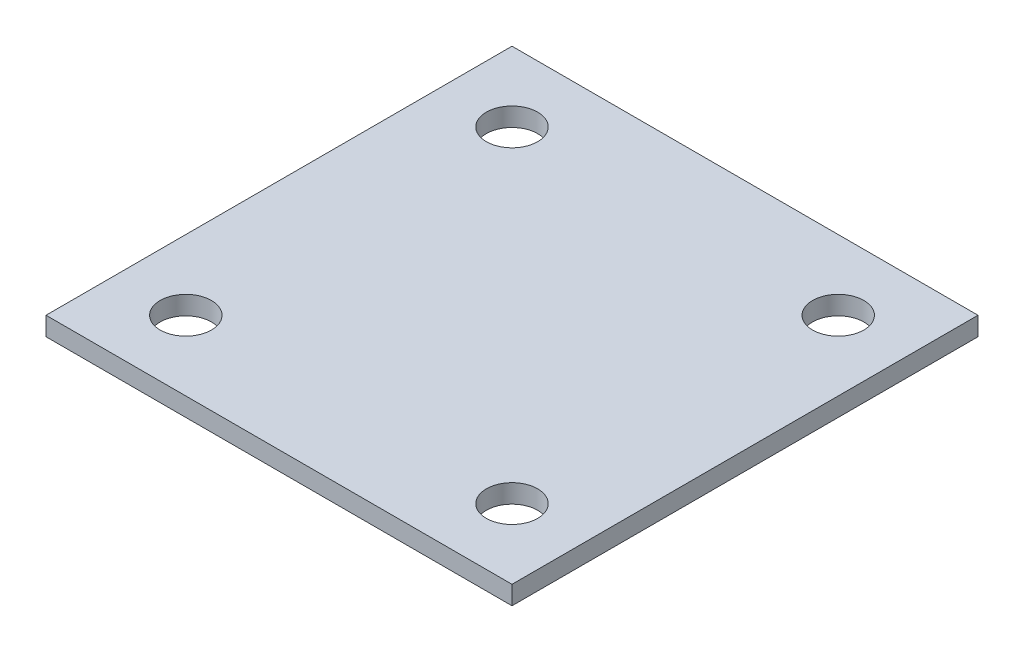
SolidWorks part; units mm, degrees
material "09Г2С ГОСТ 4543-71"
ref_plane "Спереди" through (0, 0, 0) normal (0, 0, 1) x (1, 0, 0)
ref_plane "Сверху" through (0, 0, 0) normal (0, 1, 0) x (1, 0, 0)
ref_plane "Справа" through (0, 0, 0) normal (1, 0, 0) x (0, 0, -1)
other "Configuration Table"
sketch "Эскиз1" plane through (0, 0, 0) normal (0, 1, 0) x (1, 0, 0)
  line L1 (-50, -50) -> (50, -50)
  line L2 (-50, -50) -> (-50, 50)
  line L3 (-50, 50) -> (50, 50)
  line L4 (50, -50) -> (50, 50)
  circle A0 centre (-35, -35) radius 5.5
  circle A1 centre (-35, 35) radius 5.5
  circle A2 centre (35, -35) radius 5.5
  circle A3 centre (35, 35) radius 5.5
extrude "Пластина 100х100х4, 4 отв. Ø11" add sketch "Эскиз1" along normal blind 4
